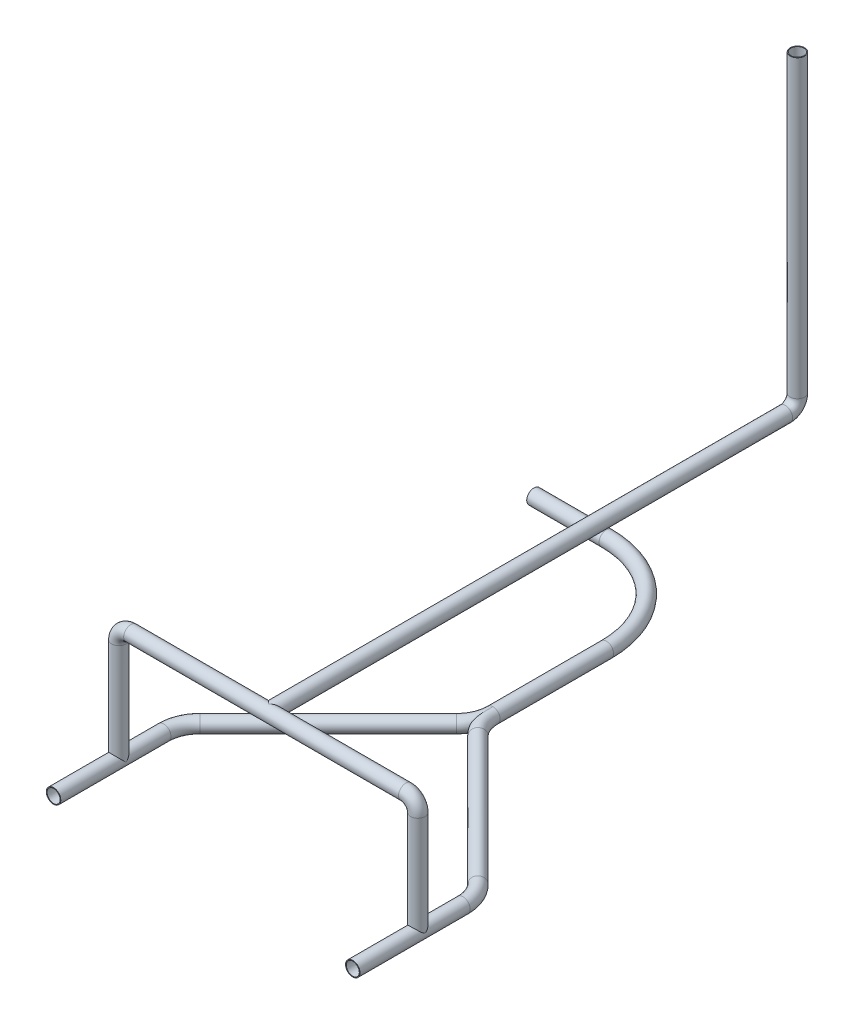
SolidWorks part; units mm, degrees
ref_plane "Front Plane" through (0, 0, 0) normal (0, 0, 1) x (1, 0, 0)
ref_plane "Top Plane" through (0, 0, 0) normal (0, 1, 0) x (1, 0, 0)
ref_plane "Right Plane" through (0, 0, 0) normal (1, 0, 0) x (0, 0, -1)
sketch3d "3DSketch5"
  line L0 (11133.0072, -1565, 449.8107) -> (11619, -1565, 449.8107) construction
  line L1 (12019, -1565, 849.8107) -> (12019, -1565, 2186) construction
  line L2 (12019, -1150, 2186) -> (12019, -2038.7174, 2186) construction
  line L3 (11619, -1565, 449.8107) -> (11319, -1565, 449.8107)
  line L4 (11319, -1565, 449.8107) -> (11319, -1564.568, 449.8107) construction
  line L5 (11319, -1564.568, 449.8107) -> (11249.4203, -1564.568, 449.8107) construction
  circle A1 centre (12019, -1150, 2186) radius 26.09 construction
  arc A2 (12019, -1565, 849.8107) -> (11619, -1565, 449.8107) centre (11619, -1565, 849.8107) ccw
  point P11 (12019, -1150, 2212.09)
  point P14 (12019, -1565, 449.8107)
  point P15 (11619, -1165, 849.8107)
  dimension "D1" = 400
sweep "Sweep-Thin2" add path "3DSketch5" circular profile diameter 60 parameters "D1"=3, "D3"=60
sketch3d "3DSketch6"
  line L0 (11399, -1226, 2250) -> (11399, -1565, 2250) construction
  line L1 (12019, -1565, 849.8107) -> (12019, -1565, 1319.7745)
  line L2 (11399, -1565, 2064.0386) -> (11399, -1565, 2520.7082)
  line L3 (12019, -1565, 849.8107) -> (12019, -1565, 2250) construction
  line L4 (12019, -1565, 2250) -> (11399, -1565, 2250) construction
  line L5 (11975.066, -1565, 1425.8406) -> (11442.934, -1565, 1957.9726)
  circle A0 centre (12019, -1565, 849.8107) radius 30 construction
  arc A1 (11442.934, -1565, 1957.9726) -> (11399, -1565, 2064.0386) centre (11549, -1565, 2064.0386) ccw
  arc A2 (12019, -1565, 1319.7745) -> (11975.066, -1565, 1425.8406) centre (11869, -1565, 1319.7745) ccw
  point P8 (12019, -1565, 879.8107)
  point P16 (11399, -1565, 2001.9066)
  point P18 (11549, -1415, 2064.0386)
  point P21 (12019, -1565, 1381.9066)
  point P22 (11869, -1715, 1319.7745)
  dimension "D2" = 150
  dimension "D1" = 135
sweep "Sweep-Thin3" add path "3DSketch6" circular profile diameter 60 parameters "D1"=3, "D3"=60
pattern_circular "CirPattern2" count 2 every 180 about axis through (12019, -1565, 849.8107) along (0, 0, 1) of bodies 105
sketch3d "3DSketch12"
  line L1 (12019, -1090, 107.8453) -> (12019, -1090, 2250)
  line L2 (12019, -1040, 57.8453) -> (12019, 183.81, 57.8453)
  line L3 (12019, 185.5713, 57.8453) -> (12019, 183.81, 57.8453) construction
  arc A0 (12019, -1040, 57.8453) -> (12019, -1090, 107.8453) centre (12019, -1040, 107.8453) ccw
  circle A3 centre (12019, 183.81, 57.8453) radius 26.09 construction
  point P11 (12019, 157.72, 57.8453)
  point P18 (12019, -1090, 57.8453)
  point P19 (11969, -1040, 107.8453)
  dimension "D2" = 50
  dimension "D1" = 1140
sweep "Sweep-Thin4" add path "3DSketch12" circular profile diameter 60 parameters "D1"=3, "D3"=60
combine bodies "Combine1" operation type add bodies to combine 106 105 104
sketch3d "3DSketch13"
  line L0 (12019, -1090, 2250) -> (11449, -1090, 2250)
  line L1 (12019, -1090, 2250) -> (12019, -1090, 107.8453) construction
  line L2 (11399, -1140, 2250) -> (11399, -1565, 2250)
  line L3 (11399, -1565, 2520.7082) -> (11399, -1565, 2250) construction
  line L4 (11399, -1565, 2064.0386) -> (11399, -1565, 2520.7082) construction
  line L5 (11399, -1565, 2250) -> (12638.028, -1565, 2250) construction
  line L6 (12019, -1090, 2250) -> (12588.028, -1090, 2250)
  line L7 (12638.028, -1565, 2250) -> (12638.028, -1140, 2250)
  arc A0 (11399, -1140, 2250) -> (11449, -1090, 2250) centre (11449, -1140, 2250) ccw
  arc A1 (12588.028, -1090, 2250) -> (12638.028, -1140, 2250) centre (12588.028, -1140, 2250) ccw
  point P12 (11399, -1090, 2250)
  point P13 (11449, -1140, 2200)
  point P16 (12638.028, -1090, 2250)
  point P17 (12588.028, -1140, 2200)
  dimension "D1" = 50
sweep "Sweep-Thin5" add path "3DSketch13" circular profile diameter 60 parameters "D1"=3, "D3"=60
